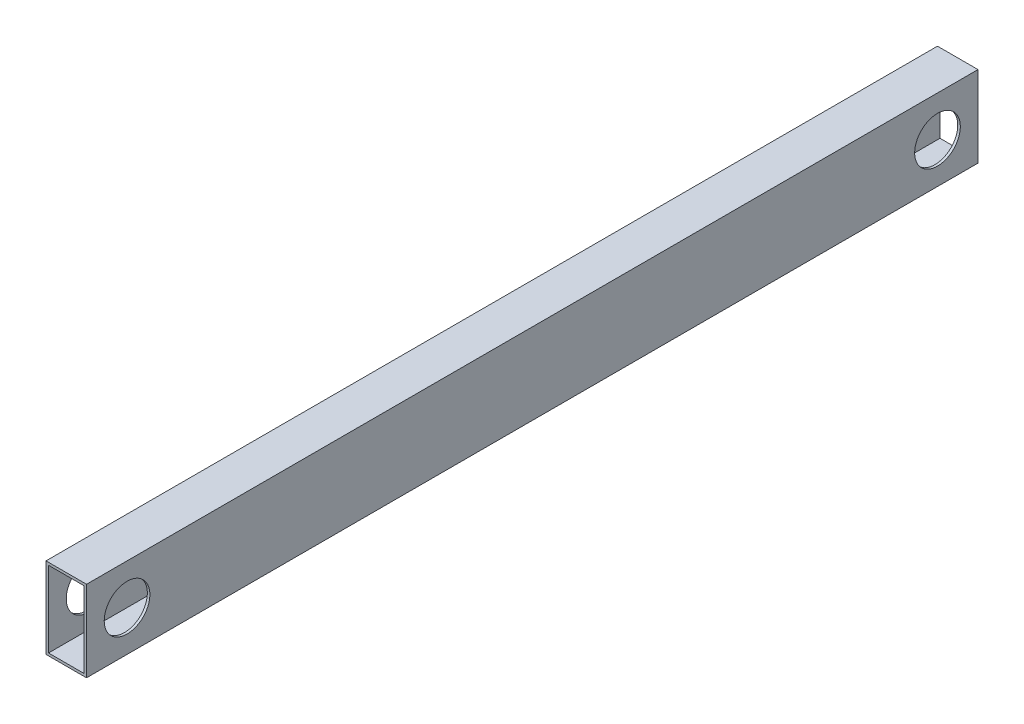
SolidWorks part; units mm, degrees
ref_plane "Front Plane" through (0, 0, 0) normal (0, 0, 1) x (1, 0, 0)
ref_plane "Top Plane" through (0, 0, 0) normal (0, 1, 0) x (1, 0, 0)
ref_plane "Right Plane" through (0, 0, 0) normal (1, 0, 0) x (0, 0, -1)
sketch "Sketch1" plane through (0, 0, 0) normal (0, 0, 1) x (1, 0, 0)
  line L0 (0, 0) -> (25.4, 50.8) construction
  line L1 (0, 0) -> (25.4, 0)
  line L2 (0, 0) -> (0, 50.8)
  line L3 (0, 50.8) -> (25.4, 50.8)
  line L4 (25.4, 0) -> (25.4, 50.8)
  line L6 (1.5875, 49.2125) -> (23.8125, 49.2125)
  line L7 (1.5875, 49.2125) -> (1.5875, 1.5875)
  line L8 (1.5875, 1.5875) -> (23.8125, 1.5875)
  line L9 (23.8125, 49.2125) -> (23.8125, 1.5875)
  line L10 (1.5875, 49.2125) -> (23.8125, 1.5875) construction
  line L11 (1.5875, 1.5875) -> (23.8125, 49.2125) construction
  point P5 (12.7, 25.4)
  point P6 (12.7, 25.4)
  dimension "D1" = 25.4
  dimension "D2" = 50.8
  dimension "D3" = 1.5875
  dimension "D4" = 1.5875
extrude "Boss-Extrude1" add sketch "Sketch1" along normal blind 558.8
sketch "Sketch2" plane through (25.4, 0, 0) normal (1, 0, 0) x (0, 0, -1)
  line L0 (0, 0) -> (0, 50.8) construction
  line L1 (-558.8, 50.8) -> (0, 50.8) construction
  line L2 (-279.4, 50.8) -> (-279.4, 104.8222) construction
  circle A0 centre (-25.4, 25.4) radius 14.3129
  circle A1 centre (-533.4, 25.4) radius 14.3129
  point P10 (-279.4, 50.8)
  point P11 (0, 0)
  dimension "D1" = 25.4
  dimension "D3" = 28.6258
  dimension "D2" = 25.4
extrude "Cut-Extrude1" cut sketch "Sketch2" against normal through all both and the other way through all
ref_plane "Plane1" through (12.7, 0, 0) normal (1, 0, 0) x (0, 0, -1)
ref_plane "Plane2" through (0, 0, 279.4) normal (0, 0, 1) x (1, 0, 0)
